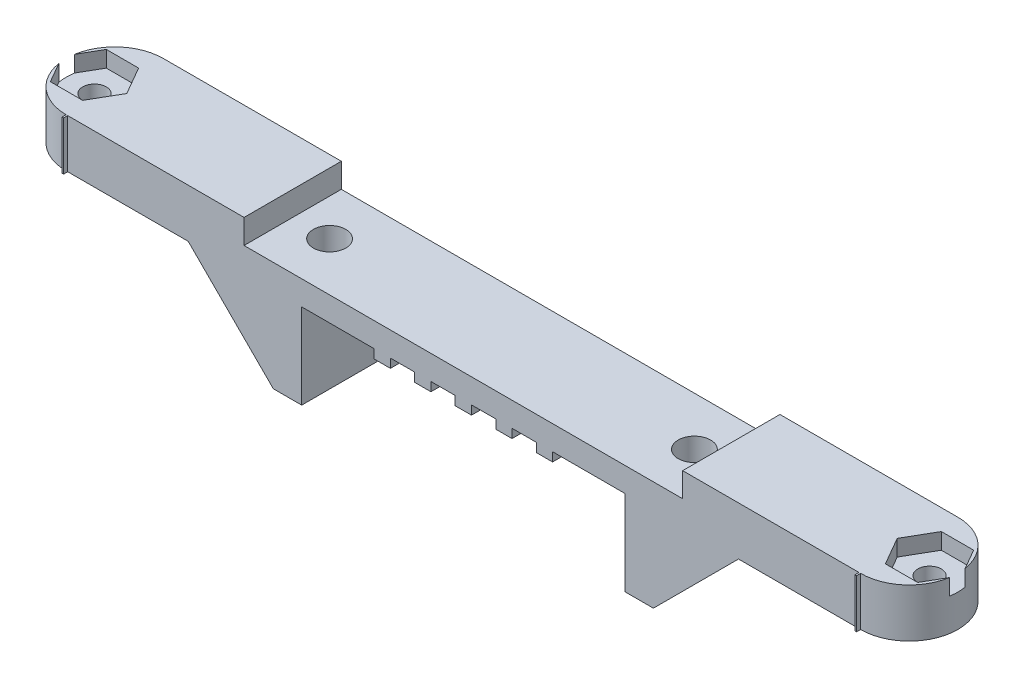
SolidWorks part; units mm, degrees
ref_plane "Front Plane" through (0, 0, 0) normal (0, 0, 1) x (1, 0, 0)
ref_plane "Top Plane" through (0, 0, 0) normal (0, 1, 0) x (1, 0, 0)
ref_plane "Right Plane" through (0, 0, 0) normal (1, 0, 0) x (0, 0, -1)
sketch "Sketch1" plane through (0, 0, 0) normal (0, 1, 0) x (1, 0, 0)
  line L0 (-49, 0) -> (49, 0) construction
  line L1 (-49, 6) -> (49, 6)
  line L2 (-49, -6) -> (49, -6)
  arc A0 (-49, 6) -> (-49, -6) centre (-49, 0) ccw
  arc A1 (49, -6) -> (49, 6) centre (49, 0) ccw
  circle A2 centre (-51.5, 0) radius 1.45
  circle A3 centre (51.5, 0) radius 1.45
  point P2 (0, 0)
  point P12 (-55, 0)
  point P13 (55, 0)
  dimension "D3" = 2.9
  dimension "D4" = 3.5
  dimension "D1" = 110
  dimension "D2" = 12
  dimension "D5" = 3.5
extrude "Boss-Extrude1" add sketch "Sketch1" along normal blind 3 contours L2 A1 L1 A0 | A2 | A3
sketch "Sketch4" plane through (0, 0, 0) normal (0, -1, 0) x (1, 0, 0)
  line L0 (-19.94, 6) -> (-19.94, -6)
  line L1 (-49, 6) -> (49, 6) construction
  line L2 (-49, -6) -> (49, -6) construction
  line L3 (-19.94, -6) -> (-23.44, -6)
  line L4 (-23.44, -6) -> (-23.44, 6)
  line L5 (-23.44, 6) -> (-19.94, 6)
  line L6 (0, 6) -> (0, -6) construction
  line L7 (-19.94, 5.075) -> (-19.94, -14.3256) construction
  line L8 (23.44, -6) -> (23.44, 6)
  line L9 (19.94, -6) -> (23.44, -6)
  line L10 (19.94, 6) -> (19.94, -6)
  line L11 (23.44, 6) -> (19.94, 6)
  dimension "D1" = 0
  dimension "D2" = 3.5
extrude "Boss-Extrude3" add sketch "Sketch4" along normal blind 10.5
sketch "Sketch5" plane through (0, 0, 0) normal (0, -1, 0) x (1, 0, 0)
  line L1 (4, 6) -> (4, -6)
  line L2 (4, 6) -> (6, 6)
  line L6 (-19.94, -6) -> (19.94, -6) construction
  line L7 (-1, 6) -> (1, 6)
  line L8 (-1, 6) -> (-1, -6)
  line L9 (-1, -6) -> (1, -6)
  line L10 (1, 6) -> (1, -6)
  line L11 (-1, 6) -> (1, -6) construction
  line L12 (-1, -6) -> (1, 6) construction
  line L13 (6, 6) -> (6, -6)
  line L14 (4, -6) -> (6, -6)
  line L15 (9, 6) -> (9, -6)
  line L16 (9, 6) -> (11, 6)
  line L17 (11, 6) -> (11, -6)
  line L18 (9, -6) -> (11, -6)
  line L19 (-4, 6) -> (-4, -6)
  line L20 (-6, -6) -> (-4, -6)
  line L21 (-6, 6) -> (-6, -6)
  line L22 (-6, 6) -> (-4, 6)
  line L23 (-9, 6) -> (-9, -6)
  line L24 (-11, -6) -> (-9, -6)
  line L25 (-11, 6) -> (-11, -6)
  line L26 (-11, 6) -> (-9, 6)
  point P0 (0, 0)
  dimension "D1" = 2
  dimension "D2" = 3
  dimension "D3" = 3
extrude "Boss-Extrude4" add sketch "Sketch5" along normal blind 1.1
sketch "Sketch6" plane through (0, 0, 6) normal (0, 0, 1) x (1, 0, 0)
  line L0 (49, 0) -> (49, 3)
  line L1 (49, 3) -> (48.8, 3)
  line L2 (-49, 3) -> (49, 3) construction
  line L3 (48.8, 3) -> (48.8, 0)
  line L4 (23.44, 0) -> (49, 0) construction
  line L5 (48.8, 0) -> (49, 0)
  line L6 (0, 0) -> (0, 3) construction
  line L7 (-48.8, 0) -> (-49, 0)
  line L8 (-48.8, 3) -> (-48.8, 0)
  line L9 (-49, 3) -> (-48.8, 3)
  line L10 (-49, 0) -> (-49, 3)
  dimension "D1" = 0.2
extrude "Boss-Extrude5" add sketch "Sketch6" along normal blind 0.5 contours L0 L1 L3 L5 | L8 L7 L10 L9
chamfer "Chamfer1" distance 10.5 2 edges at (23.44, 0, 0) (-23.44, 0, 0)
hole_wizard "Ø3.0mm Dowel Hole1" positions "Sketch7" profile "Sketch9" hole size "Ø3.0" standard "ANSI Metric" end condition up to next
sketch "Sketch7" plane through (0, 3, 0) normal (0, 1, 0) x (1, 0, 0)
  point P0 (-51.5, 0)
  point P2 (51.5, 0)
sketch "Sketch9" plane through (-51.5, 3, 0) normal (1, 0, 0) x (0, 0, 1)
  line L0 (0, 0) -> (0, 13.5)
  line L1 (0, 13.5) -> (1.45, 13.5)
  line L2 (1.45, 13.5) -> (1.45, 0)
  line L5 (1.45, 0) -> (0, 0)
  line L11 (0, -6.35) -> (0, 107.95) construction
  dimension "Thru Hole Dia." = 2.9
  dimension "Thru Hole Depth" = 13.5
sketch "Sketch10" plane through (0, 3, 0) normal (0, 1, 0) x (1, 0, 0)
  line L0 (-27.05, -6) -> (-27.05, 6)
  line L1 (27.05, -6) -> (27.05, 6)
  line L4 (27.05, -6) -> (48.8, -6)
  line L5 (-27.05, 6) -> (-49, 6)
  line L6 (-27, -44.4532) -> (-27, 21.84) construction
  line L8 (-49, -6) -> (-49, -6.5)
  line L9 (-49, -6.5) -> (-48.8, -6.5)
  line L10 (-48.8, -6.5) -> (-48.8, -6)
  line L11 (-48.8, -6) -> (48.8, -6)
  line L12 (48.8, -6) -> (48.8, -6.5)
  line L13 (48.8, -6.5) -> (49, -6.5)
  line L14 (49, -6.5) -> (49, -6)
  line L15 (49, 6) -> (-49, 6)
  line L16 (-49, -6) -> (-49, -6.5)
  line L17 (-49, -6.5) -> (-48.8, -6.5)
  line L18 (-48.8, -6.5) -> (-48.8, -6)
  line L19 (-48.8, -6) -> (-27.05, -6)
  line L20 (48.8, -6) -> (48.8, -6.5)
  line L21 (48.8, -6.5) -> (49, -6.5)
  line L22 (49, -6.5) -> (49, -6)
  line L23 (49, 6) -> (27.05, 6)
  line L24 (27, 21.84) -> (27, -44.4532) construction
  circle A1 centre (51.5, 0) radius 1.45
  arc A2 (-49, 6) -> (-49, -6) centre (-49, 0) ccw
  arc A3 (49, -6) -> (49, 6) centre (49, 0) ccw
  arc A4 (-49, 6) -> (-49, -6) centre (-49, 0) ccw
  arc A5 (49, -6) -> (49, 6) centre (49, 0) ccw
  circle A7 centre (-51.5, 0) radius 1.45
  circle A8 centre (51.5, 0) radius 1.45 construction
  line M20 (-48.8, -6) -> (48.8, -6)
  line M21 (48.8, -6) -> (48.8, -6.5)
  line M22 (48.8, -6.5) -> (49, -6.5)
  line M23 (49, -6.5) -> (49, -6)
  arc M24 (49, -6) -> (49, 6) centre (49, 0) ccw
  line M25 (49, 6) -> (-49, 6)
  circle M26 centre (51.5, 0) radius 1.45
  dimension "D4" = 2.9
  dimension "D5" = 2.9
  dimension "D2" = 0.05
  dimension "D3" = 0.05
  dimension "D1" = 0
extrude "Boss-Extrude6" add sketch "Sketch10" along normal blind 3 contours L1 M20 M21 M22 M23 M24 M25 M26 | A4 L16 L17 L18 L19 L0 L5 | A7 region at (40.1839, 3, 0.002)
sketch "Sketch11" plane through (0, 6, 0) normal (0, 1, 0) x (1, 0, 0)
  line L1 (-53.4919, 3.45) -> (-55.4837, 0)
  line L2 (-55.4837, 0) -> (-53.4919, -3.45)
  line L3 (-53.4919, -3.45) -> (-49.5081, -3.45)
  line L4 (-49.5081, -3.45) -> (-47.5163, 0)
  line L5 (-47.5163, 0) -> (-49.5081, 3.45)
  line L6 (-49.5081, 3.45) -> (-53.4919, 3.45)
  line L8 (-48.8, -6) -> (-27.05, -6) construction
  line L9 (0, 0) -> (0, -50000) construction
  line L10 (49.5081, 3.45) -> (53.4919, 3.45)
  line L11 (47.5163, 0) -> (49.5081, 3.45)
  line L12 (49.5081, -3.45) -> (47.5163, 0)
  line L13 (53.4919, -3.45) -> (49.5081, -3.45)
  line L14 (55.4837, 0) -> (53.4919, -3.45)
  line L15 (53.4919, 3.45) -> (55.4837, 0)
  circle A0 centre (-51.5, 0) radius 3.45 construction
  circle M15 centre (-51.5, 0) radius 1.45
  dimension "D1" = 6.9
extrude "Cut-Extrude1" cut sketch "Sketch11" against normal blind 2 contours L15 L10 L11 L12 L13 L14 | L5 L6 L1 L2 L3 L4 M15 region at (-51.5, 6, -3.3446) region at (51.5, 6, 0)
sketch "Sketch12" plane through (0, 3, 0) normal (0, 1, 0) x (1, 0, 0)
  circle A0 centre (-22.5, 0) radius 2 construction
  circle A1 centre (22.5, 0) radius 2 construction
  circle A2 centre (-22.5, 0) radius 2
  circle A3 centre (22.5, 0) radius 2
extrude "Cut-Extrude2" cut sketch "Sketch12" against normal blind 8
